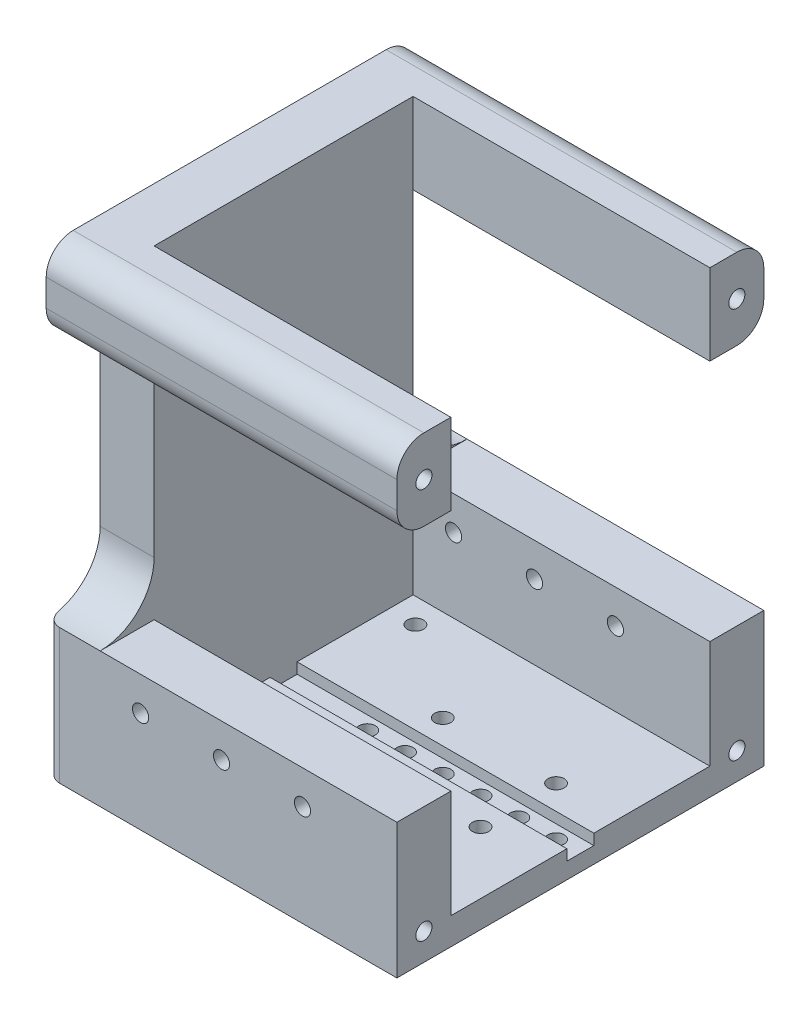
SolidWorks part; units mm, degrees
ref_plane "前视基准面" through (0, 0, 0) normal (0, 0, 1) x (1, 0, 0)
ref_plane "上视基准面" through (0, 0, 0) normal (0, 1, 0) x (1, 0, 0)
ref_plane "右视基准面" through (0, 0, 0) normal (1, 0, 0) x (0, 0, -1)
other "Configuration Table"
sketch "草图2" plane through (0, 0, 0) normal (1, 0, 0) x (0, 0, -1)
  line L1 (-1.9386, 5.1642) -> (46.0614, 5.1642)
  line L2 (-1.9386, 5.1642) -> (-1.9386, -69.8358)
  line L3 (-1.9386, -69.8358) -> (46.0614, -69.8358)
  line L4 (46.0614, 5.1642) -> (46.0614, -69.8358)
  dimension "D1" = 75
  dimension "D2" = 48
extrude "凸台-拉伸1" add sketch "草图2" along normal blind 10
sketch "草图5" plane through (10, 0, 0) normal (1, 0, 0) x (0, 0, -1)
  line L1 (46.0614, 5.1642) -> (56.0614, 5.1642)
  line L2 (46.0614, 5.1642) -> (46.0614, -4.8358)
  line L3 (46.0614, -4.8358) -> (56.0614, -4.8358)
  line L4 (56.0614, 5.1642) -> (56.0614, -4.8358)
  line L5 (46.0614, -69.8358) -> (56.0614, -69.8358)
  line L6 (46.0614, -69.8358) -> (46.0614, -49.8358)
  line L7 (46.0614, -49.8358) -> (56.0614, -49.8358)
  line L8 (56.0614, -69.8358) -> (56.0614, -49.8358)
  line L9 (-1.9386, -69.8358) -> (-11.9386, -69.8358)
  line L10 (-1.9386, -69.8358) -> (-1.9386, -49.8358)
  line L11 (-1.9386, -49.8358) -> (-11.9386, -49.8358)
  line L12 (-11.9386, -69.8358) -> (-11.9386, -49.8358)
  line L13 (-1.9386, 5.1642) -> (-11.9386, 5.1642)
  line L14 (-1.9386, 5.1642) -> (-1.9386, -4.8358)
  line L15 (-1.9386, -4.8358) -> (-11.9386, -4.8358)
  line L16 (-11.9386, 5.1642) -> (-11.9386, -4.8358)
  dimension "D1" = 10
  dimension "D2" = 20
  dimension "D3" = 10
  dimension "D4" = 20
  dimension "D5" = 10
  dimension "D6" = 10
  dimension "D7" = 10
  dimension "D8" = 10
extrude "凸台-拉伸2" add sketch "草图5" along normal blind 55 and the other way blind 10 separate body
sketch "草图6" plane through (0, -69.8358, 0) normal (0, -1, 0) x (1, 0, 0)
  line L7 (65, 1.9386) -> (65, 11.9386) construction
  line L8 (65, 11.9386) -> (0, 11.9386) construction
  line L9 (0, 11.9386) -> (0, 1.9386) construction
  line L10 (0, 1.9386) -> (0, -46.0614) construction
  line L14 (0, -56.0614) -> (65, -56.0614) construction
  line L15 (65, -56.0614) -> (65, -46.0614) construction
  line L17 (0, -46.0614) -> (0, -56.0614) construction
  line L19 (65, 1.9386) -> (65, 11.9386)
  line L20 (65, 11.9386) -> (0, 11.9386)
  line L21 (0, 11.9386) -> (0, 1.9386)
  line L22 (0, 1.9386) -> (0, -46.0614)
  line L26 (0, -56.0614) -> (65, -56.0614)
  line L27 (65, -56.0614) -> (65, -46.0614)
  line L29 (0, -46.0614) -> (0, -56.0614)
  line L30 (65, 1.9386) -> (65, -46.0614)
extrude "凸台-拉伸3" add sketch "草图6" along normal blind 5
sketch "草图7" plane through (0, 0, 0) normal (-1, 0, 0) x (0, 0, 1)
  line L0 (1.9386, -49.8358) -> (-46.0614, 5.1642) construction
  line L1 (-46.0614, 5.1642) -> (1.9386, 5.1642) construction
  line L2 (1.9386, 5.1642) -> (-46.0614, -49.8358) construction
  circle A0 centre (-22.0614, -22.3358) radius 2.5
  dimension "D1" = 5
extrude "切除-拉伸1" cut sketch "草图7" against normal blind 10
fillet "圆角1" radius 10 2 edges at (5, -49.8358, -46.0614) (5, -49.8358, 1.9386)
sketch "草图8" plane through (0, 0, -56.0614) normal (0, 0, -1) x (-1, 0, 0)
  line L0 (-65, -49.8358) -> (0, -62.3358) construction
  line L1 (0, -74.8358) -> (0, -49.8358) construction
  line L2 (0, -49.8358) -> (-65, -62.3358) construction
  line L3 (-65, -74.8358) -> (-65, -49.8358) construction
  circle A0 centre (-32.5, -56.0858) radius 1.5
  dimension "D1" = 3
extrude "切除-拉伸2" cut sketch "草图8" against normal through all contours A0
pattern_linear "阵列(线性)1" count 2 spacing 15 along (1, 0, 0) count 2 spacing 15 along (-1, 0, 0) of "切除-拉伸2"
sketch "草图10" plane through (0, -69.8358, 0) normal (0, 1, 0) x (1, 0, 0)
  circle A1 centre (15, 2.6329) radius 1.5 construction
  circle A3 centre (15, 41.49) radius 1.5 construction
  circle A5 centre (15, 2.6329) radius 1.5
  circle A7 centre (15, 41.49) radius 1.5
extrude "切除-拉伸4" cut sketch "草图10" against normal blind 10
sketch "草图11" plane through (65, 0, 0) normal (1, 0, 0) x (0, 0, -1)
  circle A0 centre (51.0614, -69.8358) radius 1.5 construction
  circle A1 centre (-6.9386, -69.8358) radius 1.5 construction
  circle A2 centre (51.0614, -69.8358) radius 1.5
  circle A3 centre (-6.9386, -69.8358) radius 1.5
extrude "切除-拉伸5" cut sketch "草图11" against normal blind 5
fillet "圆角9" radius 2.5 2 edges at (0, -62.3358, -56.0614) (0, -62.3358, 11.9386)
sketch "草图13" plane through (0, 5.1642, 0) normal (0, 1, 0) x (1, 0, 0)
  line L0 (0, -11.9386) -> (65, -11.9386) construction
  line L1 (65, -11.9386) -> (65, -1.9386) construction
  line L2 (65, -1.9386) -> (0, -1.9386) construction
  line L3 (0, -1.9386) -> (0, -11.9386) construction
  line L4 (0, 46.0614) -> (0, -1.9386) construction
  line L6 (10, -1.9386) -> (10, 46.0614) construction
  line L8 (0, 46.0614) -> (65, 46.0614) construction
  line L9 (65, 46.0614) -> (65, 56.0614) construction
  line L10 (65, 56.0614) -> (0, 56.0614) construction
  line L11 (0, 56.0614) -> (0, 46.0614) construction
  line L12 (0, -11.9386) -> (65, -11.9386)
  line L13 (65, -11.9386) -> (65, -1.9386)
  line L14 (65, -1.9386) -> (10, -1.9386)
  line L15 (0, -1.9386) -> (0, -11.9386)
  line L16 (0, 46.0614) -> (0, -1.9386)
  line L18 (10, -1.9386) -> (10, 46.0614)
  line L20 (10, 46.0614) -> (65, 46.0614)
  line L21 (65, 46.0614) -> (65, 56.0614)
  line L22 (65, 56.0614) -> (0, 56.0614)
  line L23 (0, 56.0614) -> (0, 46.0614)
extrude "凸台-拉伸5" add sketch "草图13" along normal blind 5
fillet "圆角10" radius 5 2 edges at (32.5, 10.1642, 11.9386) (32.5, -4.8358, 11.9386)
fillet "圆角11" radius 5 2 edges at (32.5, -4.8358, -56.0614) (32.5, 10.1642, -56.0614)
sketch "草图14" plane through (65, 0, 0) normal (1, 0, 0) x (0, 0, -1)
  line L0 (-6.9386, 10.1642) -> (-6.9386, -4.8358) construction
  line L1 (-1.9386, 2.6642) -> (-11.9386, 2.6642) construction
  line L2 (-1.9386, 10.1642) -> (-1.9386, -4.8358) construction
  line L3 (-11.9386, 5.1642) -> (-11.9386, 0.1642) construction
  line L4 (56.0614, 2.6642) -> (46.0614, 2.6642) construction
  line L5 (56.0614, 0.1642) -> (56.0614, 5.1642) construction
  line L6 (46.0614, 10.1642) -> (46.0614, -4.8358) construction
  line L7 (51.0614, 10.1642) -> (51.0614, -4.8358) construction
  line L8 (46.0614, -4.8358) -> (51.0614, -4.8358) construction
  circle A0 centre (-6.9386, 2.6642) radius 1.5
  circle A1 centre (51.0614, 2.6642) radius 1.5
  dimension "D1" = 3
  dimension "D2" = 3
extrude "切除-拉伸6" cut sketch "草图14" against normal blind 5
sketch "草图15" plane through (65, 0, 0) normal (1, 0, 0) x (0, 0, -1)
  line L0 (46.0614, -69.8358) -> (-1.9386, -69.8358) construction
  line L1 (19.5614, -69.8358) -> (24.5614, -69.8358)
  line L2 (19.5614, -69.8358) -> (19.5614, -71.8358)
  line L3 (19.5614, -71.8358) -> (24.5614, -71.8358)
  line L4 (24.5614, -69.8358) -> (24.5614, -71.8358)
  line L8 (46.0614, -49.8358) -> (46.0614, -69.8358) construction
  dimension "D1" = 5
  dimension "D2" = 21.5
  dimension "D3" = 2
extrude "切除-拉伸7" cut sketch "草图15" against normal up to surface (55 mm away) up to face at (10, -34.3476, -22.0614)
sketch "草图17" plane through (0, -69.8358, 0) normal (0, 1, 0) x (1, 0, 0)
  circle A0 centre (60.5, 22.0614) radius 1.5 construction
  circle A1 centre (46.5, 22.0614) radius 1.5 construction
  circle A2 centre (53.5, 29.0614) radius 1.5 construction
  circle A3 centre (53.5, 22.0614) radius 1.5 construction
  circle A4 centre (53.5, 15.0614) radius 1.5 construction
  circle A5 centre (32.5, 15.0614) radius 1.5 construction
  circle A6 centre (39.5, 22.0614) radius 1.5 construction
  circle A7 centre (25.5, 22.0614) radius 1.5 construction
  circle A8 centre (32.5, 22.0614) radius 1.5 construction
  circle A9 centre (32.5, 29.0614) radius 1.5 construction
  circle A10 centre (60.5, 22.0614) radius 1.5
  circle A11 centre (46.5, 22.0614) radius 1.5
  circle A12 centre (53.5, 29.0614) radius 1.5
  circle A13 centre (53.5, 22.0614) radius 1.5
  circle A14 centre (53.5, 15.0614) radius 1.5
  circle A15 centre (32.5, 15.0614) radius 1.5
  circle A16 centre (39.5, 22.0614) radius 1.5
  circle A17 centre (25.5, 22.0614) radius 1.5
  circle A18 centre (32.5, 22.0614) radius 1.5
  circle A19 centre (32.5, 29.0614) radius 1.5
extrude "切除-拉伸10" cut sketch "草图17" against normal through all
